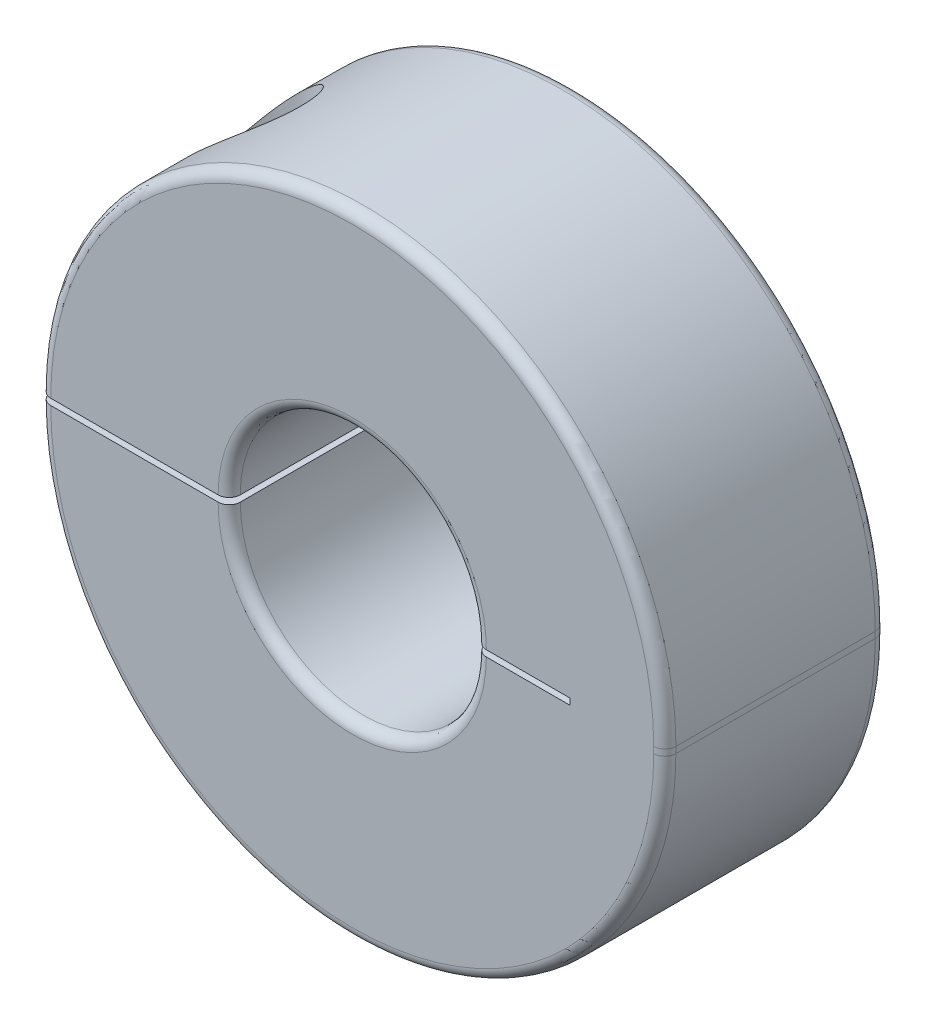
SolidWorks part; units mm, degrees
ref_plane "Front Plane" through (0, 0, 0) normal (0, 0, 1) x (1, 0, 0)
ref_plane "Top Plane" through (0, 0, 0) normal (0, 1, 0) x (1, 0, 0)
ref_plane "Right Plane" through (0, 0, 0) normal (1, 0, 0) x (0, 0, -1)
sketch "Sketch1" plane through (0, 0, 0) normal (0, 0, 1) x (1, 0, 0)
  line L0 (-12.7, 0) -> (-5, 0) construction
  line L1 (-12.7, 0.127) -> (-5, 0.127)
  line L2 (-12.7, -0.127) -> (-5, -0.127)
  line L3 (5, 0.127) -> (12.7, 0.127) construction
  line L4 (5, -0.127) -> (12.7, -0.127) construction
  line L5 (0, 0) -> (0, 12.7) construction
  line L6 (12.7, 0.127) -> (12.7, -0.127)
  line L7 (5, 0.127) -> (8.85, 0.127)
  line L8 (8.85, 0.127) -> (8.85, -0.127)
  line L10 (8.85, -0.127) -> (5, -0.127)
  circle A0 centre (0, 0) radius 12.7 construction
  circle A1 centre (0, 0) radius 5 construction
  arc A2 (-12.7, 0.127) -> (12.7, 0.127) centre (0, 0.127) cw
  arc A3 (-12.7, -0.127) -> (12.7, -0.127) centre (0, -0.127) ccw
  arc A4 (-5, 0.127) -> (5, 0.127) centre (0, 0.127) cw
  arc A5 (-5, -0.127) -> (5, -0.127) centre (0, -0.127) ccw
  point P4 (12.7, 0)
  dimension "Bore Dia" = 10
  dimension "OD" = 25.4
  dimension "Separation" = 0.254
extrude "Extrude1" add sketch "Sketch1" along normal mid plane 9
sketch "Sketch4" plane through (0, 0, 0) normal (0, 0, 1) x (1, 0, 0)
  line L0 (-8.85, 12.827) -> (-6.6, 12.827)
  line L1 (-6.6, 12.827) -> (-6.6, 1.627)
  line L2 (-6.6, 1.627) -> (-7.35, 1.627)
  line L3 (-7.35, 1.627) -> (-7.35, -12.827)
  line L4 (-7.35, -12.827) -> (-8.85, -12.827)
  line L5 (-8.85, -12.827) -> (-8.85, 12.827)
  line L6 (-6.6, 4.627) -> (-11.1, 4.627) construction
  line L7 (-8.85, 12.827) -> (-8.85, 15.367) construction
  line L8 (-6.6, 12.827) -> (0, 12.827) construction
  line L9 (0, -12.827) -> (-7.35, -12.827) construction
  line L10 (-12.7, 0) -> (-5, 0) construction
  line L11 (-12.7, 0.127) -> (-5, 0.127) construction
  circle A0 centre (0, 0) radius 12.7 construction
  arc A1 (12.7, 0.127) -> (-12.7, 0.127) centre (0, 0.127) ccw construction
  circle A2 centre (0, 0) radius 5 construction
  arc A3 (-12.7, -0.127) -> (12.7, -0.127) centre (0, -0.127) ccw construction
  point P13 (-8.85, 0)
  point P19 (-8.85, 0)
  point P20 (-8.85, 4.627)
  dimension "D1" = 3
  dimension "D2" = 7.7
  dimension "D3" = 1.5
  dimension "D4" = 4.5
  dimension "D5" = 2.54
  dimension "Screw Dia" = 3
revolve "Cut-Revolve1" cut sketch "Sketch4" angle 360 about L5
sketch "Sketch6" plane through (0, 0, 0) normal (0, 0, 1) x (1, 0, 0)
  line L0 (-8.85, 4.627) -> (-6.6, 4.627)
  line L1 (-6.6, 4.627) -> (-11.1, 4.627) construction
  line L2 (-6.6, 4.627) -> (-6.6, 1.627)
  line L3 (-6.6, 1.627) -> (-7.35, 1.627)
  line L4 (-7.35, 1.627) -> (-7.35, -4.373)
  line L5 (-7.35, 1.627) -> (-7.35, -12.827) construction
  line L6 (-7.35, -4.373) -> (-8.85, -4.373)
  line L7 (-8.85, -12.827) -> (-8.85, 12.827) construction
  line L8 (-8.85, -4.373) -> (-8.85, 4.627)
  line L9 (-7.35, -4.373) -> (-10.35, -4.373) construction
  dimension "Head Ht" = 3
  dimension "Screw Lg" = 9
revolve "Revolve1" add sketch "Sketch6" angle 360 about L8
sketch "Sketch7" plane through (0, 4.627, 0) normal (0, 1, 0) x (-1, 0, 0)
  line L1 (8.85, -1.3856) -> (10.05, -0.6928)
  line L2 (10.05, -0.6928) -> (10.05, 0.6928)
  line L3 (10.05, 0.6928) -> (8.85, 1.3856)
  line L4 (8.85, 1.3856) -> (7.65, 0.6928)
  line L5 (7.65, 0.6928) -> (7.65, -0.6928)
  line L6 (7.65, -0.6928) -> (8.85, -1.3856)
  circle A0 centre (8.85, 0) radius 1.2 construction
  dimension "D1" = 2.4
extrude "Cut-Extrude2" cut sketch "Sketch7" against normal blind 1.5
fillet "Fillet1" radius 0.45 8 edges at (0, 5.127, -4.5) (0, 5.127, 4.5) (0, 12.827, -4.5) (0, 12.827, 4.5) (0, -12.827, -4.5) (0, -12.827, 4.5) (12.7, 0, -4.5) (12.7, 0, 4.5)
fillet "Fillet2" radius 0.45 2 edges at (0, -5.127, -4.5) (0, -5.127, 4.5)
chamfer "Chamfer2" distance 0.254 angle 45 1 edges at (-8.85, 4.627, -2.25)
equation "\"D1@Sketch4\" = \"Screw Dia@Sketch4\""
equation "\"D4@Sketch4\" = \"Screw Dia@Sketch4\"*1.5"
equation "\"D1@Sketch7\" = \"Screw Dia@Sketch4\"*.8"
equation "\"D1@Cut-Extrude2\" = \"Head Ht@Sketch6\"/2"
equation "\"D3@Sketch4\" = \"D1@Sketch4\"*.5"
equation "\"D1@Fillet1\" = \"Width@Extrude1\"*.05"
equation "\"D1@Fillet2\" = \"D1@Fillet1\""
equation "\"Screw Lg@Sketch6\" = \"Head Ht@Sketch6\"*3"
equation "\"Separation@Sketch1\" = \"OD@Sketch1\"*.01"
